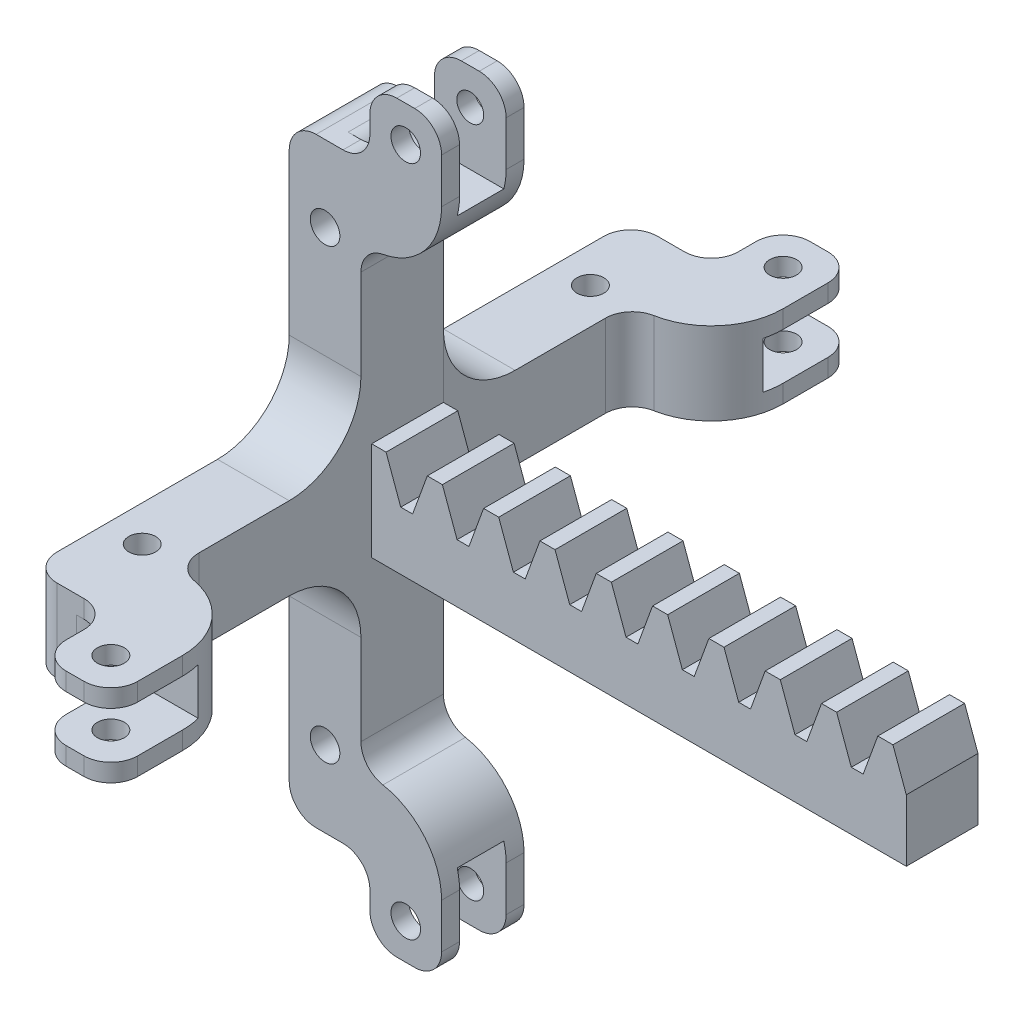
SolidWorks part; units mm, degrees
ref_plane "前视基准面" through (0, 0, 0) normal (0, 0, 1) x (1, 0, 0)
ref_plane "上视基准面" through (0, 0, 0) normal (0, 1, 0) x (1, 0, 0)
ref_plane "右视基准面" through (0, 0, 0) normal (1, 0, 0) x (0, 0, -1)
sketch "草图1" plane through (0, 0, 0) normal (0, 0, 1) x (1, 0, 0)
  line L1 (0, 0) -> (188.4956, 0)
  line L2 (0, 0) -> (0, -10)
  line L3 (0, -10) -> (188.4956, -10)
  line L4 (188.4956, 0) -> (188.4956, -10)
  dimension "D1" = 10
  dimension "L" = 188.4956
extrude "拉伸1" add sketch "草图1" along normal blind 5
sketch "草图2" plane through (0, 0, 5) normal (0, 0, 1) x (1, 0, 0)
  line L0 (0, 0) -> (1.6379, 4.5)
  line L1 (1.6379, 4.5) -> (3.3236, 4.5)
  line L2 (3.3236, 4.5) -> (4.9614, 0)
  line L3 (188.4956, 0) -> (0, 0) construction
  line L4 (0, 0) -> (4.9614, 0)
  line L5 (0.9099, 2.5) -> (4.0515, 2.5) construction
  dimension "D2" = 70
  dimension "alpha" = 110
  dimension "ha" = 2
  dimension "hf" = 2.5
  dimension "S" = 3.1416
extrude "拉伸2" add sketch "草图2" against normal up to surface (5 mm away) up to face at (94.2478, -5, 0)
pattern_linear "阵列(线性)1" count 30 spacing 6.2832 along (1, 0, 0) of "拉伸2"
ref_plane "基准面1" through (188.4956, -10, 0) normal (0, 0, -1) x (-1, 0, 0)
sketch "草图3" plane through (188.4956, -10, 0) normal (0, 0, -1) x (-1, 0, 0)
  line L123 (188.4956, 0) -> (188.4956, 10)
  line L124 (188.4956, 10) -> (186.8577, 14.5)
  line L125 (186.8577, 14.5) -> (185.172, 14.5)
  line L126 (185.172, 14.5) -> (183.5341, 10)
  line L127 (183.5341, 10) -> (182.2124, 10)
  line L128 (182.2124, 10) -> (180.5745, 14.5)
  line L129 (180.5745, 14.5) -> (178.8888, 14.5)
  line L130 (178.8888, 14.5) -> (177.2509, 10)
  line L131 (177.2509, 10) -> (175.9292, 10)
  line L132 (175.9292, 10) -> (174.2913, 14.5)
  line L133 (174.2913, 14.5) -> (172.6056, 14.5)
  line L134 (172.6056, 14.5) -> (170.9677, 10)
  line L135 (170.9677, 10) -> (169.646, 10)
  line L136 (169.646, 10) -> (168.0081, 14.5)
  line L137 (168.0081, 14.5) -> (166.3224, 14.5)
  line L138 (166.3224, 14.5) -> (164.6846, 10)
  line L139 (164.6846, 10) -> (163.3628, 10)
  line L140 (163.3628, 10) -> (161.725, 14.5)
  line L141 (161.725, 14.5) -> (160.0392, 14.5)
  line L142 (160.0392, 14.5) -> (158.4014, 10)
  line L143 (158.4014, 10) -> (157.0796, 10)
  line L144 (157.0796, 10) -> (155.4418, 14.5)
  line L145 (155.4418, 14.5) -> (153.7561, 14.5)
  line L146 (153.7561, 14.5) -> (152.1182, 10)
  line L147 (152.1182, 10) -> (150.7964, 10)
  line L148 (150.7964, 10) -> (149.1586, 14.5)
  line L149 (149.1586, 14.5) -> (147.4729, 14.5)
  line L150 (147.4729, 14.5) -> (145.835, 10)
  line L151 (145.835, 10) -> (144.5133, 10)
  line L152 (144.5133, 10) -> (142.8754, 14.5)
  line L153 (142.8754, 14.5) -> (141.1897, 14.5)
  line L154 (141.1897, 14.5) -> (139.5518, 10)
  line L155 (139.5518, 10) -> (138.2301, 10)
  line L156 (138.2301, 10) -> (136.5922, 14.5)
  line L157 (136.5922, 14.5) -> (134.9065, 14.5)
  line L158 (134.9065, 14.5) -> (133.2686, 10)
  line L159 (133.2686, 10) -> (131.9469, 10)
  line L160 (131.9469, 10) -> (130.309, 14.5)
  line L161 (130.309, 14.5) -> (128.6233, 14.5)
  line L162 (128.6233, 14.5) -> (126.9854, 10)
  line L163 (126.9854, 10) -> (125.6637, 10)
  line L164 (125.6637, 10) -> (124.0258, 14.5)
  line L165 (124.0258, 14.5) -> (122.3401, 14.5)
  line L166 (122.3401, 14.5) -> (120.7023, 10)
  line L167 (120.7023, 10) -> (119.3805, 10)
  line L168 (119.3805, 10) -> (117.7427, 14.5)
  line L169 (117.7427, 14.5) -> (116.0569, 14.5)
  line L170 (116.0569, 14.5) -> (114.4191, 10)
  line L171 (114.4191, 10) -> (113.0973, 10)
  line L172 (113.0973, 10) -> (111.4595, 14.5)
  line L173 (111.4595, 14.5) -> (109.7738, 14.5)
  line L174 (109.7738, 14.5) -> (108.1359, 10)
  line L175 (108.1359, 10) -> (106.8142, 10)
  line L176 (106.8142, 10) -> (105.1763, 14.5)
  line L177 (105.1763, 14.5) -> (103.4906, 14.5)
  line L178 (103.4906, 14.5) -> (101.8527, 10)
  line L179 (101.8527, 10) -> (100.531, 10)
  line L180 (100.531, 10) -> (98.8931, 14.5)
  line L181 (98.8931, 14.5) -> (97.2074, 14.5)
  line L182 (97.2074, 14.5) -> (95.5695, 10)
  line L183 (95.5695, 10) -> (94.2478, 10)
  line L184 (94.2478, 10) -> (92.6099, 14.5)
  line L185 (92.6099, 14.5) -> (90.9242, 14.5)
  line L186 (90.9242, 14.5) -> (89.2863, 10)
  line L187 (89.2863, 10) -> (87.9646, 10)
  line L188 (87.9646, 10) -> (86.3267, 14.5)
  line L189 (86.3267, 14.5) -> (84.641, 14.5)
  line L190 (84.641, 14.5) -> (83.0032, 10)
  line L191 (83.0032, 10) -> (81.6814, 10)
  line L192 (81.6814, 10) -> (80.0435, 14.5)
  line L193 (80.0435, 14.5) -> (78.3578, 14.5)
  line L194 (78.3578, 14.5) -> (76.72, 10)
  line L195 (76.72, 10) -> (75.3982, 10)
  line L196 (75.3982, 10) -> (73.7604, 14.5)
  line L197 (73.7604, 14.5) -> (72.0746, 14.5)
  line L198 (72.0746, 14.5) -> (70.4368, 10)
  line L199 (70.4368, 10) -> (69.115, 10)
  line L200 (69.115, 10) -> (67.4772, 14.5)
  line L201 (67.4772, 14.5) -> (65.7915, 14.5)
  line L202 (65.7915, 14.5) -> (64.1536, 10)
  line L203 (64.1536, 10) -> (62.8319, 10)
  line L204 (62.8319, 10) -> (61.194, 14.5)
  line L205 (61.194, 14.5) -> (59.5083, 14.5)
  line L206 (59.5083, 14.5) -> (57.8704, 10)
  line L207 (57.8704, 10) -> (56.5487, 10)
  line L208 (56.5487, 10) -> (54.9108, 14.5)
  line L209 (54.9108, 14.5) -> (53.2251, 14.5)
  line L210 (53.2251, 14.5) -> (51.5872, 10)
  line L211 (51.5872, 10) -> (50.2655, 10)
  line L212 (50.2655, 10) -> (48.6276, 14.5)
  line L213 (48.6276, 14.5) -> (46.9419, 14.5)
  line L214 (46.9419, 14.5) -> (45.304, 10)
  line L215 (45.304, 10) -> (43.9823, 10)
  line L216 (43.9823, 10) -> (42.3444, 14.5)
  line L217 (42.3444, 14.5) -> (40.6587, 14.5)
  line L218 (40.6587, 14.5) -> (39.0209, 10)
  line L219 (39.0209, 10) -> (37.6991, 10)
  line L220 (37.6991, 10) -> (36.0612, 14.5)
  line L221 (36.0612, 14.5) -> (34.3755, 14.5)
  line L222 (34.3755, 14.5) -> (32.7377, 10)
  line L223 (32.7377, 10) -> (31.4159, 10)
  line L224 (31.4159, 10) -> (29.7781, 14.5)
  line L225 (29.7781, 14.5) -> (28.0923, 14.5)
  line L226 (28.0923, 14.5) -> (26.4545, 10)
  line L227 (26.4545, 10) -> (25.1327, 10)
  line L228 (25.1327, 10) -> (23.4949, 14.5)
  line L229 (23.4949, 14.5) -> (21.8092, 14.5)
  line L230 (21.8092, 14.5) -> (20.1713, 10)
  line L231 (20.1713, 10) -> (18.8496, 10)
  line L232 (18.8496, 10) -> (17.2117, 14.5)
  line L233 (17.2117, 14.5) -> (15.526, 14.5)
  line L234 (15.526, 14.5) -> (13.8881, 10)
  line L235 (13.8881, 10) -> (12.5664, 10)
  line L236 (12.5664, 10) -> (10.9285, 14.5)
  line L237 (10.9285, 14.5) -> (9.2428, 14.5)
  line L238 (9.2428, 14.5) -> (7.6049, 10)
  line L239 (7.6049, 10) -> (6.2832, 10)
  line L240 (6.2832, 10) -> (4.6453, 14.5)
  line L241 (4.6453, 14.5) -> (2.9596, 14.5)
  line L242 (2.9596, 14.5) -> (1.3217, 10)
  line L243 (1.3217, 10) -> (0, 10)
  line L244 (0, 10) -> (0, 0)
  line L245 (0, 0) -> (188.4956, 0)
  line L246 (188.4956, 0) -> (188.4956, 10)
  line L247 (188.4956, 10) -> (186.8577, 14.5)
  line L248 (186.8577, 14.5) -> (185.172, 14.5)
  line L249 (185.172, 14.5) -> (183.5341, 10)
  line L250 (183.5341, 10) -> (182.2124, 10)
  line L251 (182.2124, 10) -> (180.5745, 14.5)
  line L252 (180.5745, 14.5) -> (178.8888, 14.5)
  line L253 (178.8888, 14.5) -> (177.2509, 10)
  line L254 (177.2509, 10) -> (175.9292, 10)
  line L255 (175.9292, 10) -> (174.2913, 14.5)
  line L256 (174.2913, 14.5) -> (172.6056, 14.5)
  line L257 (172.6056, 14.5) -> (170.9677, 10)
  line L258 (170.9677, 10) -> (169.646, 10)
  line L259 (169.646, 10) -> (168.0081, 14.5)
  line L260 (168.0081, 14.5) -> (166.3224, 14.5)
  line L261 (166.3224, 14.5) -> (164.6846, 10)
  line L262 (164.6846, 10) -> (163.3628, 10)
  line L263 (163.3628, 10) -> (161.725, 14.5)
  line L264 (161.725, 14.5) -> (160.0392, 14.5)
  line L265 (160.0392, 14.5) -> (158.4014, 10)
  line L266 (158.4014, 10) -> (157.0796, 10)
  line L267 (157.0796, 10) -> (155.4418, 14.5)
  line L268 (155.4418, 14.5) -> (153.7561, 14.5)
  line L269 (153.7561, 14.5) -> (152.1182, 10)
  line L270 (152.1182, 10) -> (150.7964, 10)
  line L271 (150.7964, 10) -> (149.1586, 14.5)
  line L272 (149.1586, 14.5) -> (147.4729, 14.5)
  line L273 (147.4729, 14.5) -> (145.835, 10)
  line L274 (145.835, 10) -> (144.5133, 10)
  line L275 (144.5133, 10) -> (142.8754, 14.5)
  line L276 (142.8754, 14.5) -> (141.1897, 14.5)
  line L277 (141.1897, 14.5) -> (139.5518, 10)
  line L278 (139.5518, 10) -> (138.2301, 10)
  line L279 (138.2301, 10) -> (136.5922, 14.5)
  line L280 (136.5922, 14.5) -> (134.9065, 14.5)
  line L281 (134.9065, 14.5) -> (133.2686, 10)
  line L282 (133.2686, 10) -> (131.9469, 10)
  line L283 (131.9469, 10) -> (130.309, 14.5)
  line L284 (130.309, 14.5) -> (128.6233, 14.5)
  line L285 (128.6233, 14.5) -> (126.9854, 10)
  line L286 (126.9854, 10) -> (125.6637, 10)
  line L287 (125.6637, 10) -> (124.0258, 14.5)
  line L288 (124.0258, 14.5) -> (122.3401, 14.5)
  line L289 (122.3401, 14.5) -> (120.7023, 10)
  line L290 (120.7023, 10) -> (119.3805, 10)
  line L291 (119.3805, 10) -> (117.7427, 14.5)
  line L292 (117.7427, 14.5) -> (116.0569, 14.5)
  line L293 (116.0569, 14.5) -> (114.4191, 10)
  line L294 (114.4191, 10) -> (113.0973, 10)
  line L295 (113.0973, 10) -> (111.4595, 14.5)
  line L296 (111.4595, 14.5) -> (109.7738, 14.5)
  line L297 (109.7738, 14.5) -> (108.1359, 10)
  line L298 (108.1359, 10) -> (106.8142, 10)
  line L299 (106.8142, 10) -> (105.1763, 14.5)
  line L300 (105.1763, 14.5) -> (103.4906, 14.5)
  line L301 (103.4906, 14.5) -> (101.8527, 10)
  line L302 (101.8527, 10) -> (100.531, 10)
  line L303 (100.531, 10) -> (98.8931, 14.5)
  line L304 (98.8931, 14.5) -> (97.2074, 14.5)
  line L305 (97.2074, 14.5) -> (95.5695, 10)
  line L306 (95.5695, 10) -> (94.2478, 10)
  line L307 (94.2478, 10) -> (92.6099, 14.5)
  line L308 (92.6099, 14.5) -> (90.9242, 14.5)
  line L309 (90.9242, 14.5) -> (89.2863, 10)
  line L310 (89.2863, 10) -> (87.9646, 10)
  line L311 (87.9646, 10) -> (86.3267, 14.5)
  line L312 (86.3267, 14.5) -> (84.641, 14.5)
  line L313 (84.641, 14.5) -> (83.0032, 10)
  line L314 (83.0032, 10) -> (81.6814, 10)
  line L315 (81.6814, 10) -> (80.0435, 14.5)
  line L316 (80.0435, 14.5) -> (78.3578, 14.5)
  line L317 (78.3578, 14.5) -> (76.72, 10)
  line L318 (76.72, 10) -> (75.3982, 10)
  line L319 (75.3982, 10) -> (73.7604, 14.5)
  line L320 (73.7604, 14.5) -> (72.0746, 14.5)
  line L321 (72.0746, 14.5) -> (70.4368, 10)
  line L322 (70.4368, 10) -> (69.115, 10)
  line L323 (69.115, 10) -> (67.4772, 14.5)
  line L324 (67.4772, 14.5) -> (65.7915, 14.5)
  line L325 (65.7915, 14.5) -> (64.1536, 10)
  line L326 (64.1536, 10) -> (62.8319, 10)
  line L327 (62.8319, 10) -> (61.194, 14.5)
  line L328 (61.194, 14.5) -> (59.5083, 14.5)
  line L329 (59.5083, 14.5) -> (57.8704, 10)
  line L330 (57.8704, 10) -> (56.5487, 10)
  line L331 (56.5487, 10) -> (54.9108, 14.5)
  line L332 (54.9108, 14.5) -> (53.2251, 14.5)
  line L333 (53.2251, 14.5) -> (51.5872, 10)
  line L334 (51.5872, 10) -> (50.2655, 10)
  line L335 (50.2655, 10) -> (48.6276, 14.5)
  line L336 (48.6276, 14.5) -> (46.9419, 14.5)
  line L337 (46.9419, 14.5) -> (45.304, 10)
  line L338 (45.304, 10) -> (43.9823, 10)
  line L339 (43.9823, 10) -> (42.3444, 14.5)
  line L340 (42.3444, 14.5) -> (40.6587, 14.5)
  line L341 (40.6587, 14.5) -> (39.0209, 10)
  line L342 (39.0209, 10) -> (37.6991, 10)
  line L343 (37.6991, 10) -> (36.0612, 14.5)
  line L344 (36.0612, 14.5) -> (34.3755, 14.5)
  line L345 (34.3755, 14.5) -> (32.7377, 10)
  line L346 (32.7377, 10) -> (31.4159, 10)
  line L347 (31.4159, 10) -> (29.7781, 14.5)
  line L348 (29.7781, 14.5) -> (28.0923, 14.5)
  line L349 (28.0923, 14.5) -> (26.4545, 10)
  line L350 (26.4545, 10) -> (25.1327, 10)
  line L351 (25.1327, 10) -> (23.4949, 14.5)
  line L352 (23.4949, 14.5) -> (21.8092, 14.5)
  line L353 (21.8092, 14.5) -> (20.1713, 10)
  line L354 (20.1713, 10) -> (18.8496, 10)
  line L355 (18.8496, 10) -> (17.2117, 14.5)
  line L356 (17.2117, 14.5) -> (15.526, 14.5)
  line L357 (15.526, 14.5) -> (13.8881, 10)
  line L358 (13.8881, 10) -> (12.5664, 10)
  line L359 (12.5664, 10) -> (10.9285, 14.5)
  line L360 (10.9285, 14.5) -> (9.2428, 14.5)
  line L361 (9.2428, 14.5) -> (7.6049, 10)
  line L362 (7.6049, 10) -> (6.2832, 10)
  line L363 (6.2832, 10) -> (4.6453, 14.5)
  line L364 (4.6453, 14.5) -> (2.9596, 14.5)
  line L365 (2.9596, 14.5) -> (1.3217, 10)
  line L366 (1.3217, 10) -> (0, 10)
  line L367 (0, 10) -> (0, 0)
  line L368 (0, 0) -> (188.4956, 0)
  dimension "D1" = 0
extrude "凸台-拉伸1" add sketch "草图3" along normal blind 3
sketch "草图5" plane through (0, -10, 0) normal (0, -1, 0) x (1, 0, 0)
  line L4 (0, 5) -> (0, -3)
  line L5 (0, -3) -> (188.4956, -3)
  line L6 (188.4956, -3) -> (188.4956, 5)
  line L7 (188.4956, 5) -> (0, 5)
  line L8 (0, 5) -> (0, -3)
  line L9 (0, -3) -> (188.4956, -3)
  line L10 (188.4956, -3) -> (188.4956, 5)
  line L11 (188.4956, 5) -> (0, 5)
  dimension "D1" = 0
extrude "切除-拉伸1" cut sketch "草图5" against normal blind 3.5
sketch "草图6" plane through (0, 0, -3) normal (0, 0, -1) x (-1, 0, 0)
  line L0 (0, -6.5) -> (-188.4956, -6.5) construction
  line L1 (-188.4956, 0) -> (-187.1738, 0)
  line L2 (-188.4956, 0) -> (-188.4956, -6.5)
  line L3 (-188.4956, -6.5) -> (-187.1738, -6.5)
  line L4 (-187.1738, 0) -> (-187.1738, -6.5)
extrude "切除-拉伸2" cut sketch "草图6" against normal up to surface (8 mm away) up to face at (94.5371, 2.0711, 5)
sketch "草图7" plane through (0, 0, 0) normal (-1, 0, 0) x (0, 0, 1)
  line L0 (1, 4.5) -> (1, -6.5) construction
  line L1 (-3, 4.5) -> (5, 4.5) construction
  line L2 (5, -6.5) -> (-3, -6.5) construction
  line L3 (5, 0) -> (5, -6.5) construction
  line L4 (-3, 32.5) -> (5, 32.5)
  line L5 (-3, 32.5) -> (-3, -34.5)
  line L6 (-3, -34.5) -> (5, -34.5)
  line L7 (5, 32.5) -> (5, -34.5)
  line L8 (-3, 32.5) -> (5, -34.5) construction
  line L9 (-3, -34.5) -> (5, 32.5) construction
  point P6 (1, -1)
  dimension "D1" = 67
extrude "凸台-拉伸2" add sketch "草图7" against normal blind 8
sketch "草图8" plane through (0, 0, 5) normal (0, 0, 1) x (1, 0, 0)
  line L1 (0, 32.5) -> (8, 32.5)
  line L2 (0, 32.5) -> (0, -34.5)
  line L3 (0, -34.5) -> (8, -34.5)
  line L4 (8, 32.5) -> (8, -34.5)
extrude "凸台-拉伸3" add sketch "草图8" along normal blind 1.2
sketch "草图9" plane through (0, 0, 6.2) normal (0, 0, 1) x (1, 0, 0)
  line L0 (0, 32.5) -> (0, -34.5) construction
  line L1 (0, -1) -> (8, -1) construction
  line L2 (8, -6.5) -> (8, 4.5) construction
  line L3 (8, 32.5) -> (0, 32.5) construction
  circle A0 centre (4, 24) radius 1.65
  circle A1 centre (4, -26) radius 1.65
  point P12 (4, 32.5)
  dimension "D1" = 3.3
  dimension "D2" = 25
extrude "切除-拉伸3" cut sketch "草图9" against normal blind 47
sketch "草图11" plane through (0, 0, 5) normal (0, 0, 1) x (1, 0, 0)
  line L1 (187.1738, -6.5) -> (97.1738, -6.5)
  line L2 (187.1738, -6.5) -> (187.1738, 12.9313)
  line L3 (187.1738, 12.9313) -> (97.1738, 12.9313)
  line L4 (97.1738, -6.5) -> (97.1738, 12.9313)
  dimension "D1" = 90
extrude "切除-拉伸5" cut sketch "草图11" against normal blind 18.5
sketch "草图12" plane through (0, 0, 5) normal (0, 0, 1) x (1, 0, 0)
  line L1 (97.1738, -6.5) -> (67.6458, -6.5)
  line L2 (97.1738, -6.5) -> (97.1738, 6.021)
  line L3 (97.1738, 6.021) -> (67.6458, 6.021)
  line L4 (67.6458, -6.5) -> (67.6458, 6.021)
extrude "切除-拉伸6" cut sketch "草图12" against normal blind 18.5
fillet "圆角1" radius 3 4 edges at (0, -34.5, 1.6) (8, -34.5, 1.6) (0, 32.5, 1.6) (8, 32.5, 1.6)
sketch "草图13" plane through (0, 0, 6.2) normal (0, 0, 1) x (1, 0, 0)
  line L0 (5, 32.5) -> (9, 32.5)
  line L2 (9, 32.5) -> (9, 40.5)
  line L3 (9, 40.5) -> (17, 40.5)
  line L4 (17, 40.5) -> (17, 24.5)
  line L5 (17, 24.5) -> (8, 24.5)
  line L6 (8, -31.5) -> (8, 29.5) construction
  line L7 (8, 29.5) -> (8, 24.5)
  line L8 (0, -1) -> (-4.4347, -1) construction
  line L9 (0, 29.5) -> (0, -31.5) construction
  line L10 (8, -31.5) -> (8, -26.5)
  line L11 (17, -26.5) -> (8, -26.5)
  line L12 (17, -42.5) -> (17, -26.5)
  line L13 (9, -42.5) -> (17, -42.5)
  line L14 (9, -34.5) -> (9, -42.5)
  line L15 (5, -34.5) -> (9, -34.5)
  arc A0 (8, 29.5) -> (5, 32.5) centre (5, 29.5) ccw construction
  arc A1 (8, 29.5) -> (5, 32.5) centre (5, 29.5) ccw
  arc A2 (8, -31.5) -> (5, -34.5) centre (5, -31.5) cw
  dimension "D1" = 8
  dimension "D2" = 8
  dimension "D3" = 1
  dimension "D4" = 8
extrude "凸台-拉伸5" add sketch "草图13" against normal up to surface (9.2 mm away) up to face at (32.3025, 1.4164, -3)
sketch "草图14" plane through (0, 0, 6.2) normal (0, 0, 1) x (1, 0, 0)
  line L0 (0, -1) -> (-5.5344, -1) construction
  line L1 (0, 29.5) -> (0, -31.5) construction
  line L2 (17, 40.5) -> (9, 40.5) construction
  circle A0 centre (13, 36.5) radius 1.65
  circle A1 centre (4, 24) radius 1.65 construction
  circle A2 centre (13, -38.5) radius 1.65
  point P8 (13, 40.5)
  dimension "D1" = 4
extrude "切除-拉伸7" cut sketch "草图14" against normal blind 10
fillet "圆角2" radius 8 2 edges at (17, 24.5, 1.6) (17, -26.5, 1.6)
fillet "圆角3" radius 3 8 edges at (9, 32.5, 1.6) (9, 40.5, 1.6) (17, 40.5, 1.6) (8, 24.5, 1.6) (8, -26.5, 1.6) (9, -34.5, 1.6) (9, -42.5, 1.6) (17, -42.5, 1.6)
sketch "草图15" plane through (0, 40.5, 0) normal (0, 1, 0) x (1, 0, 0)
  line L0 (12, 3) -> (12, -6.2) construction
  line L1 (6.5695, 1) -> (19.4305, 1)
  line L2 (6.5695, 1) -> (6.5695, -4.2)
  line L3 (6.5695, -4.2) -> (19.4305, -4.2)
  line L4 (19.4305, 1) -> (19.4305, -4.2)
  line L5 (6.5695, 1) -> (19.4305, -4.2) construction
  line L6 (6.5695, -4.2) -> (19.4305, 1) construction
  line L7 (14, 3) -> (12, 3) construction
  point P0 (13, -1.6)
  point P7 (12, -1.6)
  point P10 (13, 3)
  dimension "D1" = 5.2
extrude "切除-拉伸8" cut sketch "草图15" against normal blind 10
fillet "圆角4" radius 2 1 edges at (6.5695, 32.5545, 1.6)
fillet "圆角5" radius 2 1 edges at (6.5695, 30.5, 1.6)
sketch "草图16" plane through (0, -42.5, 0) normal (0, -1, 0) x (1, 0, 0)
  line L1 (8, 4.2) -> (18, 4.2)
  line L2 (8, 4.2) -> (8, -1)
  line L3 (8, -1) -> (18, -1)
  line L4 (18, 4.2) -> (18, -1)
  line L5 (8, 4.2) -> (18, -1) construction
  line L6 (8, -1) -> (18, 4.2) construction
  line L8 (12, 6.2) -> (14, 6.2) construction
  line L9 (12, 6.2) -> (12, -3) construction
  point P0 (13, 1.6)
  point P17 (13, 6.2)
  point P20 (12, 1.6)
  dimension "D1" = 10
  dimension "D2" = 5.2
extrude "切除-拉伸9" cut sketch "草图16" against normal blind 10
fillet "圆角6" radius 3 1 edges at (8, -35.2639, 1.6)
fillet "圆角7" radius 3 1 edges at (8, -32.5, 1.6)
sketch "草图17" plane through (0, 0, -3) normal (0, 0, -1) x (-1, 0, 0)
  circle A0 centre (-13, -38.5) radius 1.65 construction
  circle A1 centre (-13, 36.5) radius 1.65 construction
  circle A2 centre (-13, -38.5) radius 1.65
  circle A3 centre (-13, 36.5) radius 1.65
  circle A4 centre (-13, 36.5) radius 1.5
  circle A5 centre (-13, -38.5) radius 1.5
  dimension "D1" = 3
extrude "凸台-拉伸6" add sketch "草图17" against normal up to surface (2 mm away) up to face at (11.2412, -36.7376, -1)
sketch "草图18" plane through (0, 0, 0) normal (-1, 0, 0) x (0, 0, 1)
  line L0 (-3, -1) -> (6.2, -1) construction
  line L1 (-3, -31.5) -> (-3, 29.5) construction
  line L2 (6.2, 29.5) -> (6.2, -31.5) construction
  line L4 (-31.9, 3.6) -> (35.1, 3.6)
  line L5 (-31.9, 3.6) -> (-31.9, -5.6)
  line L6 (-31.9, -5.6) -> (35.1, -5.6)
  line L7 (35.1, 3.6) -> (35.1, -5.6)
  line L8 (-31.9, 3.6) -> (35.1, -5.6) construction
  line L9 (-31.9, -5.6) -> (35.1, 3.6) construction
  point P6 (1.6, -1)
  dimension "D1" = 9.2
  dimension "D2" = 67
extrude "凸台-拉伸7" add sketch "草图18" against normal up to surface (8 mm away) up to face at (8, -1, 1.3)
sketch "草图19" plane through (0, -42.5, 0) normal (0, -1, 0) x (1, 0, 0)
  line L0 (8, -31.9) -> (0, -31.9) construction
  line L1 (9, -39.9) -> (17, -39.9)
  line L2 (9, -39.9) -> (9, -23.9) construction
  line L3 (9, -23.9) -> (17, -23.9)
  line L4 (17, -39.9) -> (17, -23.9)
  line L5 (8, -3) -> (8, -31.9) construction
  line L6 (8, -31.9) -> (9, -31.9)
  line L7 (8, -23.9) -> (9, -23.9)
  line L8 (8, -23.9) -> (8, -31.9)
  line L9 (9, -31.9) -> (9, -39.9)
  line L10 (0, 35.1) -> (0, -31.9) construction
  line L11 (0, 1.6) -> (-8.3404, 1.6) construction
  line L12 (9, 35.1) -> (9, 43.1)
  line L13 (8, 27.1) -> (8, 35.1)
  line L14 (8, 27.1) -> (9, 27.1)
  line L15 (8, 35.1) -> (9, 35.1)
  line L16 (17, 43.1) -> (17, 27.1)
  line L17 (9, 27.1) -> (17, 27.1)
  line L18 (9, 43.1) -> (17, 43.1)
  dimension "D1" = 8
  dimension "D2" = 8
  dimension "D3" = 8
  dimension "D4" = 1
extrude "凸台-拉伸8" add sketch "草图19" against normal up to surface (46.1 mm away) up to face at (4, 3.6, 20.65)
sketch "草图20" plane through (0, 0, 0) normal (-1, 0, 0) x (0, 0, 1)
  line L1 (-23.9, -5.6) -> (-68.0354, -5.6)
  line L2 (-23.9, -5.6) -> (-23.9, -56.0906)
  line L3 (-23.9, -56.0906) -> (-68.0354, -56.0906)
  line L4 (-68.0354, -5.6) -> (-68.0354, -56.0906)
  line L5 (27.1, -5.6) -> (55.2867, -5.6)
  line L6 (27.1, -5.6) -> (27.1, -46.3192)
  line L7 (27.1, -46.3192) -> (55.2867, -46.3192)
  line L8 (55.2867, -5.6) -> (55.2867, -46.3192)
extrude "切除-拉伸10" cut sketch "草图20" against normal blind 33
sketch "草图21" plane through (0, -5.6, 0) normal (0, -1, 0) x (1, 0, 0)
  line L0 (17, 43.1) -> (9, 43.1) construction
  line L1 (17, 27.1) -> (17, -23.9) construction
  line L2 (17, 1.6) -> (75.4731, 1.6) construction
  circle A0 centre (13, 39.1) radius 1.5
  circle A1 centre (13, -35.9) radius 1.5
  point P4 (13, 43.1)
  dimension "D2" = 3
  dimension "D1" = 4
extrude "切除-拉伸11" cut sketch "草图21" against normal blind 33
sketch "草图22" plane through (0, 0, 43.1) normal (0, 0, 1) x (1, 0, 0)
  line L0 (17, 3.6) -> (9, 3.6) construction
  line L1 (8, 1.6) -> (18, 1.6)
  line L2 (8, 1.6) -> (8, -3.6)
  line L3 (8, -3.6) -> (18, -3.6)
  line L4 (18, 1.6) -> (18, -3.6)
  line L5 (8, 1.6) -> (18, -3.6) construction
  line L6 (8, -3.6) -> (18, 1.6) construction
  line L7 (17, 3.6) -> (17, -5.6) construction
  point P0 (13, -1)
  point P7 (13, 3.6)
  point P10 (17, -1)
  dimension "D1" = 10
  dimension "D2" = 5.2
extrude "切除-拉伸12" cut sketch "草图22" against normal blind 10
sketch "草图23" plane through (0, 0, -39.9) normal (0, 0, -1) x (-1, 0, 0)
  line L4 (-8, 1.6) -> (-17, 1.6)
  line L5 (-8, -3.6) -> (-8, 1.6)
  line L6 (-17, -3.6) -> (-8, -3.6)
  line L7 (-17, 1.6) -> (-17, -3.6)
  line L8 (-8, 1.6) -> (-17, 1.6)
  line L9 (-8, -3.6) -> (-8, 1.6)
  line L10 (-17, -3.6) -> (-8, -3.6)
  line L11 (-17, 1.6) -> (-17, -3.6)
  dimension "D1" = 0
extrude "切除-拉伸13" cut sketch "草图23" against normal blind 10
fillet "圆角8" radius 3 12 edges at (8, -1, -31.9) (8, -1, 35.1) (9, 2.6, 43.1) (9, -4.6, 43.1) (17, -4.6, 43.1) (17, 2.6, 43.1) (9, 2.6, -39.9) (9, -4.6, -39.9) (17, -4.6, -39.9) (17, 2.6, -39.9) (0, -1, -31.9) (0, -1, 35.1)
fillet "圆角9" radius 3 2 edges at (8, -1, 33.1) (8, -1, -29.9)
fillet "圆角10" radius 8 2 edges at (17, -1, -23.9) (17, -1, 27.1)
fillet "圆角11" radius 3 2 edges at (8, -1, -23.9) (8, -1, 27.1)
fillet "圆角12" radius 8 4 edges at (4, -5.6, 6.2) (4, -5.6, -3) (4, 3.6, -3) (4, 3.6, 6.2)
sketch "草图24" plane through (0, 3.6, 0) normal (0, 1, 0) x (1, 0, 0)
  line L0 (0, 11) -> (8, 11) construction
  line L1 (0, 28.9) -> (0, -32.1) construction
  line L2 (0, -1.6) -> (-5.7682, -1.6) construction
  circle A0 centre (4, 23.4) radius 1.5
  circle A1 centre (4, -26.6) radius 1.5
  point P4 (4, 11)
  dimension "D1" = 3
  dimension "D2" = 25
extrude "切除-拉伸14" cut sketch "草图24" against normal blind 10
fillet "圆角13" radius 3 4 edges at (9, -4.6, 35.1) (9, 2.6, 35.1) (9, -4.6, -31.9) (9, 2.6, -31.9)
equation "\"d\"=\"S@草图2\" * 2"
equation "\"z\"= int(  \"L@草图1\" / (  \"S@草图2\" * 2 ) + 0.5 )"
